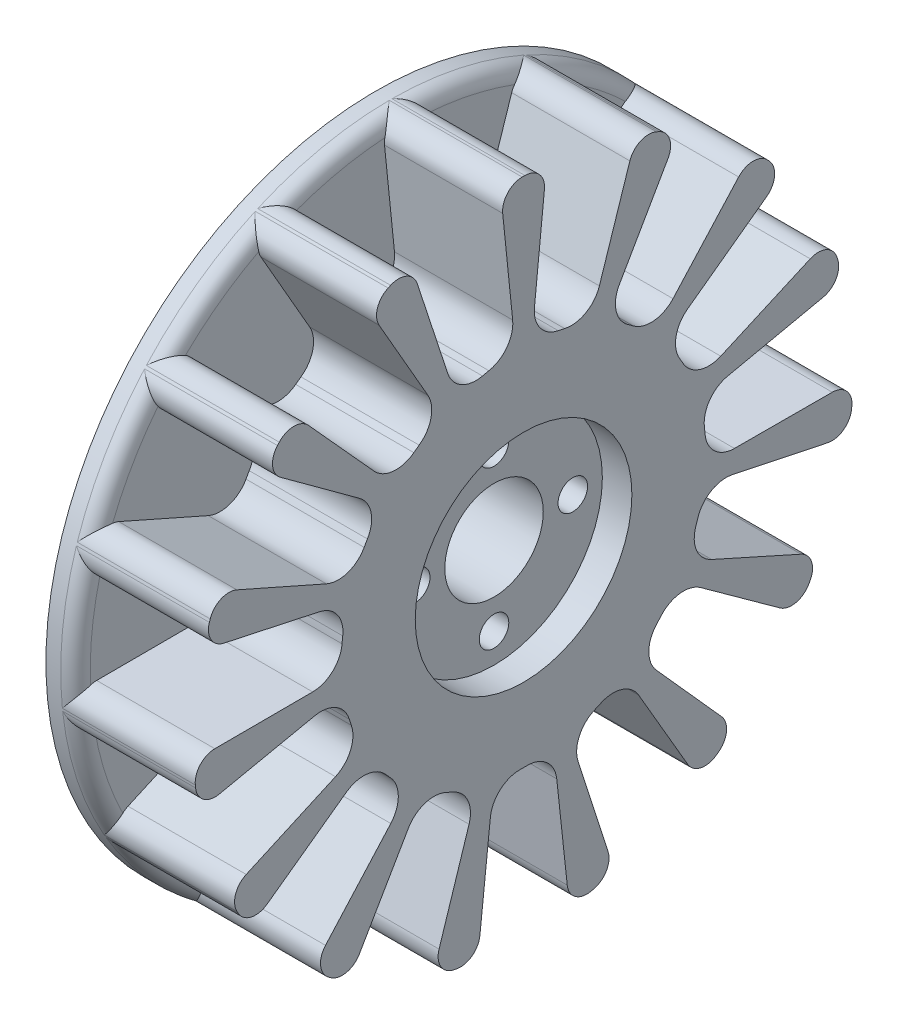
SolidWorks part; units mm, degrees
ref_plane "Front Plane" through (0, 0, 0) normal (0, 0, 1) x (1, 0, 0)
ref_plane "Top Plane" through (0, 0, 0) normal (0, 1, 0) x (1, 0, 0)
ref_plane "Right Plane" through (0, 0, 0) normal (1, 0, 0) x (0, 0, -1)
sketch "Semi_sprocket" plane through (0, 0, 0) normal (1, 0, 0) x (0, 0, -1)
  circle A0 centre (0, 0) radius 33.5
  dimension "D1" = 67
extrude "Estrusione-Estrusione2" add sketch "Semi_sprocket" along normal blind 15
sketch "Teeth" plane through (15, 0, 0) normal (1, 0, 0) x (0, 0, -1)
  line L0 (0, 0) -> (0, 33.5) construction
  line L1 (0, 0) -> (13.6257, 30.6038) construction
  line L2 (0, 0) -> (24.8954, 22.4159) construction
  line L3 (0, 0) -> (31.8604, 10.3521) construction
  line L4 (0, 0) -> (33.3165, -3.5017) construction
  line L5 (0, 0) -> (29.0119, -16.75) construction
  line L6 (0, 0) -> (19.6908, -27.1021) construction
  line L7 (0, 0) -> (6.965, -32.7679) construction
  line L8 (0, 0) -> (-6.965, -32.7679) construction
  line L9 (0, 0) -> (-19.6908, -27.1021) construction
  line L10 (0, 0) -> (-29.0119, -16.75) construction
  line L11 (0, 0) -> (-33.3165, -3.5017) construction
  line L12 (0, 0) -> (-31.8604, 10.3521) construction
  line L13 (0, 0) -> (-24.8954, 22.4159) construction
  line L14 (0, 0) -> (-13.6257, 30.6038) construction
  line L15 (102.025, 198.2078) -> (797.3584, 198.2078) construction
  line L16 (0.807, 18.4824) -> (0, 0) construction
  line L17 (6.7803, 17.2127) -> (0, 0) construction
  line L18 (6.965, 32.7679) -> (0, 0) construction
  line L19 (2.3368, 33.4184) -> (0, 0) construction
  line L20 (11.4577, 31.4797) -> (0, 0) construction
  line L21 (2.3368, 33.4184) -> (0.807, 18.4824)
  line L22 (6.7803, 17.2127) -> (11.4577, 31.4797)
  line L23 (15.7273, 29.5787) -> (8.2547, 16.5563)
  line L24 (13.1951, 12.9668) -> (23.2711, 24.0979)
  line L25 (26.3984, 20.6247) -> (14.2751, 11.7674)
  line L26 (17.3284, 6.4788) -> (31.0607, 12.5493)
  line L27 (32.5049, 8.1044) -> (17.8272, 4.9439)
  line L28 (18.4655, -1.1294) -> (33.4796, -1.1691)
  line L29 (32.9911, -5.8172) -> (18.2968, -2.7345)
  line L30 (16.4097, -8.5423) -> (30.1096, -14.6854)
  line L31 (27.7728, -18.733) -> (15.6027, -9.94)
  line L32 (11.5165, -14.4783) -> (21.5334, -25.6625)
  line L33 (17.7523, -28.4096) -> (10.2108, -15.4269)
  line L34 (4.632, -17.9107) -> (9.2339, -32.2023)
  line L35 (4.6623, -33.174) -> (3.0534, -18.2463)
  line L36 (-3.0534, -18.2463) -> (-4.6623, -33.174)
  line L37 (-9.2339, -32.2023) -> (-4.632, -17.9107)
  line L38 (-10.2108, -15.4269) -> (-17.7523, -28.4096)
  line L39 (-21.5334, -25.6625) -> (-11.5165, -14.4783)
  line L40 (-15.6027, -9.94) -> (-27.7728, -18.733)
  line L41 (-30.1096, -14.6854) -> (-16.4097, -8.5423)
  line L42 (-18.2968, -2.7345) -> (-32.9911, -5.8172)
  line L43 (-33.4796, -1.1691) -> (-18.4655, -1.1294)
  line L44 (-17.8272, 4.9439) -> (-32.5049, 8.1044)
  line L45 (-31.0607, 12.5493) -> (-17.3284, 6.4788)
  line L46 (-14.2751, 11.7674) -> (-26.3984, 20.6247)
  line L47 (-23.2711, 24.0979) -> (-13.1951, 12.9668)
  line L48 (-8.2547, 16.5563) -> (-15.7273, 29.5787)
  line L49 (-11.4577, 31.4797) -> (-6.7803, 17.2127)
  line L50 (-0.807, 18.4824) -> (-2.3368, 33.4184)
  circle A0 centre (0, 0) radius 33.5 construction
  circle A1 centre (0, 0) radius 18.5 construction
  arc A2 (0, 33.5) -> (13.6257, 30.6038) centre (0, 0) cw construction
  arc A3 (2.3368, 33.4184) -> (11.4577, 31.4797) centre (0, 0) cw
  arc A4 (0.807, 18.4824) -> (6.7803, 17.2127) centre (0, 0) cw
  arc A5 (8.2547, 16.5563) -> (13.1951, 12.9668) centre (0, 0) cw
  arc A6 (15.7273, 29.5787) -> (23.2711, 24.0979) centre (0, 0) cw
  arc A7 (14.2751, 11.7674) -> (17.3284, 6.4788) centre (0, 0) cw
  arc A8 (26.3984, 20.6247) -> (31.0607, 12.5493) centre (0, 0) cw
  arc A9 (17.8272, 4.9439) -> (18.4655, -1.1294) centre (0, 0) cw
  arc A10 (32.5049, 8.1044) -> (33.4796, -1.1691) centre (0, 0) cw
  arc A11 (18.2968, -2.7345) -> (16.4097, -8.5423) centre (0, 0) cw
  arc A12 (32.9911, -5.8172) -> (30.1096, -14.6854) centre (0, 0) cw
  arc A13 (15.6027, -9.94) -> (11.5165, -14.4783) centre (0, 0) cw
  arc A14 (27.7728, -18.733) -> (21.5334, -25.6625) centre (0, 0) cw
  arc A15 (10.2108, -15.4269) -> (4.632, -17.9107) centre (0, 0) cw
  arc A16 (17.7523, -28.4096) -> (9.2339, -32.2023) centre (0, 0) cw
  arc A17 (3.0534, -18.2463) -> (-3.0534, -18.2463) centre (0, 0) cw
  arc A18 (4.6623, -33.174) -> (-4.6623, -33.174) centre (0, 0) cw
  arc A19 (-4.632, -17.9107) -> (-10.2108, -15.4269) centre (0, 0) cw
  arc A20 (-9.2339, -32.2023) -> (-17.7523, -28.4096) centre (0, 0) cw
  arc A21 (-11.5165, -14.4783) -> (-15.6027, -9.94) centre (0, 0) cw
  arc A22 (-21.5334, -25.6625) -> (-27.7728, -18.733) centre (0, 0) cw
  arc A23 (-16.4097, -8.5423) -> (-18.2968, -2.7345) centre (0, 0) cw
  arc A24 (-30.1096, -14.6854) -> (-32.9911, -5.8172) centre (0, 0) cw
  arc A25 (-18.4655, -1.1294) -> (-17.8272, 4.9439) centre (0, 0) cw
  arc A26 (-33.4796, -1.1691) -> (-32.5049, 8.1044) centre (0, 0) cw
  arc A27 (-17.3284, 6.4788) -> (-14.2751, 11.7674) centre (0, 0) cw
  arc A28 (-31.0607, 12.5493) -> (-26.3984, 20.6247) centre (0, 0) cw
  arc A29 (-13.1951, 12.9668) -> (-8.2547, 16.5563) centre (0, 0) cw
  arc A30 (-23.2711, 24.0979) -> (-15.7273, 29.5787) centre (0, 0) cw
  arc A31 (-6.7803, 17.2127) -> (-0.807, 18.4824) centre (0, 0) cw
  arc A32 (-11.4577, 31.4797) -> (-2.3368, 33.4184) centre (0, 0) cw
  point P23 (0, 0)
  point P89 (0, 0)
  dimension "D3" = 2.5
  dimension "D4" = 2.5
  dimension "D5" = 4
  dimension "D6" = 4
  dimension "D7" = 15.0142
  dimension "D8" = 15.0142
  dimension "D9" = 15.0142
  dimension "D10" = 14.936
  dimension "D12" = 15
  dimension "D2" = 15
  dimension "D11" = 15
extrude "Taglio-Estrusione1" cut sketch "Teeth" against normal blind 12
sketch "Hub_hole" plane through (15, 0, 0) normal (1, 0, 0) x (0, 0, -1)
  circle A0 centre (0, 0) radius 11
  dimension "D1" = 22
extrude "Taglio-Estrusione2" cut sketch "Hub_hole" against normal blind 3
sketch "Hub_fix" plane through (12, 0, 0) normal (1, 0, 0) x (0, 0, -1)
  line L0 (0, 0) -> (0, 11) construction
  circle A0 centre (0, 0) radius 5
  circle A1 centre (0, 0) radius 11 construction
  circle A2 centre (0, 8) radius 1.5
  circle A3 centre (8, 0) radius 1.5
  circle A4 centre (0, -8) radius 1.5
  circle A5 centre (-8, 0) radius 1.5
  point P18 (0, 0)
  dimension "D1" = 10
  dimension "D2" = 3
  dimension "D3" = 8
extrude "Taglio-Estrusione3" cut sketch "Hub_fix" against normal through all
fillet "Raccordo3" radius 1.5 15 edges at (3, 27.1021, 19.6908) (3, 16.75, 29.0119) (3, 3.5017, 33.3165) (3, -10.3521, 31.8604) (3, -22.4159, 24.8954) (3, -30.6038, 13.6257) (3, -33.5, 0) (3, -30.6038, -13.6257) (3, -22.4159, -24.8954) (3, -10.3521, -31.8604) (3, 3.5017, -33.3165) (3, 16.75, -29.0119) (3, 27.1021, -19.6908) (3, 32.7679, -6.965) (3, 32.7679, 6.965)
sketch "Schizzo1" plane through (15, 0, 0) normal (1, 0, 0) x (0, 0, -1)
  circle A0 centre (0, 0) radius 21
  circle A1 centre (0, 0) radius 11 construction
  circle A2 centre (0, 0) radius 33.245
  dimension "D1" = 10
extrude "Taglio-Estrusione4" [suppressed] cut sketch "Schizzo1" against normal blind 12
fillet "Raccordo7" radius 2 30 edges at (8.25, 12.5493, 31.0607) (8.25, 8.1044, 32.5049) (8.25, -1.1691, 33.4796) (8.25, -5.8172, 32.9911) (8.25, -14.6854, 30.1096) (8.25, -18.733, 27.7728) (8.25, -25.6625, 21.5334) (8.25, -28.4096, 17.7523) (8.25, -32.2023, 9.2339) (8.25, -33.174, 4.6623) (8.25, -33.174, -4.6623) (8.25, -32.2023, -9.2339) (8.25, -28.4096, -17.7523) (8.25, -25.6625, -21.5334) (8.25, -18.733, -27.7728) (8.25, -14.6854, -30.1096) (8.25, -5.8172, -32.9911) (8.25, -1.1691, -33.4796) (8.25, 8.1044, -32.5049) (8.25, 12.5493, -31.0607) (8.25, 20.6247, -26.3984) (8.25, 24.0979, -23.2711) (8.25, 29.5787, -15.7273) (8.25, 31.4797, -11.4577) (8.25, 33.4184, -2.3368) (8.25, 33.4184, 2.3368) (8.25, 31.4797, 11.4577) (8.25, 29.5787, 15.7273) (8.25, 24.0979, 23.2711) (8.25, 20.6247, 26.3984)
fillet "Raccordo8" radius 3 30 edges at (9, 12.9668, 13.1951) (9, 11.7674, 14.2751) (9, 6.4788, 17.3284) (9, 4.9439, 17.8272) (9, -1.1294, 18.4655) (9, -2.7345, 18.2968) (9, -8.5423, 16.4097) (9, -9.94, 15.6027) (9, -14.4783, 11.5165) (9, -15.4269, 10.2108) (9, -17.9107, 4.632) (9, -18.2463, 3.0534) (9, -18.2463, -3.0534) (9, -17.9107, -4.632) (9, -15.4269, -10.2108) (9, -14.4783, -11.5165) (9, -9.94, -15.6027) (9, -8.5423, -16.4097) (9, -2.7345, -18.2968) (9, -1.1294, -18.4655) (9, 4.9439, -17.8272) (9, 6.4788, -17.3284) (9, 11.7674, -14.2751) (9, 12.9668, -13.1951) (9, 16.5563, -8.2547) (9, 17.2127, -6.7803) (9, 18.4824, -0.807) (9, 18.4824, 0.807) (9, 17.2127, 6.7803) (9, 16.5563, 8.2547)
mirror "Specchia1" [suppressed] about plane through (0, 0, 0) normal (1, 0, 0)
equation "\"D4@Teeth\" = \"D3@Teeth\""
equation "\"D6@Teeth\" = \"D5@Teeth\""
